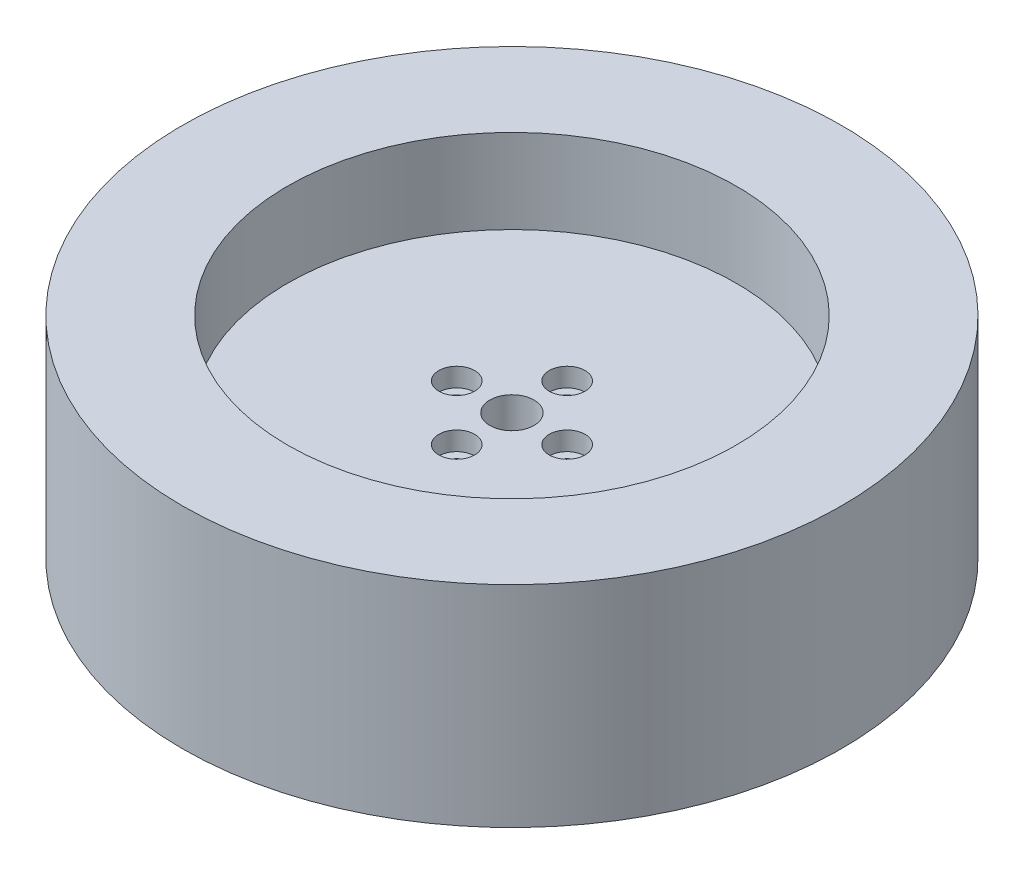
SolidWorks part; units mm, degrees
material "1060 Alloy"
ref_plane "Front Plane" through (0, 0, 0) normal (0, 0, 1) x (1, 0, 0)
ref_plane "Top Plane" through (0, 0, 0) normal (0, 1, 0) x (1, 0, 0)
ref_plane "Right Plane" through (0, 0, 0) normal (1, 0, 0) x (0, 0, -1)
sketch "Sketch1" plane through (0, 0, 0) normal (0, 1, 0) x (1, 0, 0)
  circle A0 centre (0, 0) radius 59.69
  dimension "D1" = 119.38
extrude "Boss-Extrude1" add sketch "Sketch1" along normal blind 19.05 and the other way blind 19.05
sketch "Sketch2" plane through (0, -19.05, 0) normal (0, -1, 0) x (1, 0, 0)
  circle A0 centre (0, 0) radius 40.64
  dimension "D1" = 81.28
extrude "Cut-Extrude2" cut sketch "Sketch2" against normal blind 15.24
sketch "Sketch13" plane through (0, 19.05, 0) normal (0, 1, 0) x (1, 0, 0)
  circle A0 centre (0, 0) radius 40.64
  dimension "D1" = 81.28
extrude "Cut-Extrude7" cut sketch "Sketch13" against normal blind 15.24
sketch "Sketch6" plane through (0, 3.81, 0) normal (0, 1, 0) x (1, 0, 0)
  line L0 (0, 0) -> (0, -60) construction
  circle A0 centre (0, 0) radius 59.69 construction
  circle A1 centre (0, -10) radius 1.7
  dimension "D1" = 10
  dimension "D2" = 3.4
sketch "Sketch7" plane through (0, 3.81, 0) normal (0, 1, 0) x (1, 0, 0)
  circle A0 centre (0, 0) radius 4
  dimension "D1" = 8
extrude "Cut-Extrude6" cut sketch "Sketch7" against normal blind 25
extrude "Cut-Extrude5" cut sketch "Sketch6" against normal blind 10 contours A1
pattern_circular "CirPattern2" count 4 over 360 about axis through (0, 3.81, 0) along (0, 1, 0) of "Cut-Extrude5", "Cut-Extrude6"
sketch "Sketch12" plane through (0, 3.81, 0) normal (0, 1, 0) x (1, 0, 0)
  point P0 (0, -10)
  point P4 (10, 0)
  point P7 (0, 10)
  point P10 (-10, 0)
hole_wizard "CBORE for M3 Hex Socket Head Cap Screw1" positions "Sketch12" profile "Sketch11" counterbore size "M3" standard "ISO"
sketch "Sketch11" plane through (0, 3.81, 10) normal (1, 0, 0) x (0, 0, 1)
  line L0 (0, 0) -> (0, 6.0215)
  line L1 (0, 6.0215) -> (1.7, 5)
  line L2 (1.7, 5) -> (1.7, 3.4)
  line L3 (1.7, 3.4) -> (3.25, 3.4)
  line L4 (3.25, 3.4) -> (3.25, 0)
  line L5 (3.25, 0) -> (0, 0)
  line L10 (0, 6.0215) -> (-1.7, 5) construction
  line L11 (0, -6.35) -> (0, 107.95) construction
  dimension "Hole Dia." = 3.4
  dimension "Hole Depth" = 5
  dimension "C'Bore Dia." = 6.5
  dimension "C'Bore Depth" = 3.4
  dimension "Drill Angle" = 118
sketch "Sketch14" plane through (0, -3.81, 0) normal (0, -1, 0) x (1, 0, 0)
  circle A0 centre (0, 0) radius 15
  dimension "D1" = 30
extrude "Cut-Extrude8" cut sketch "Sketch14" against normal blind 2
